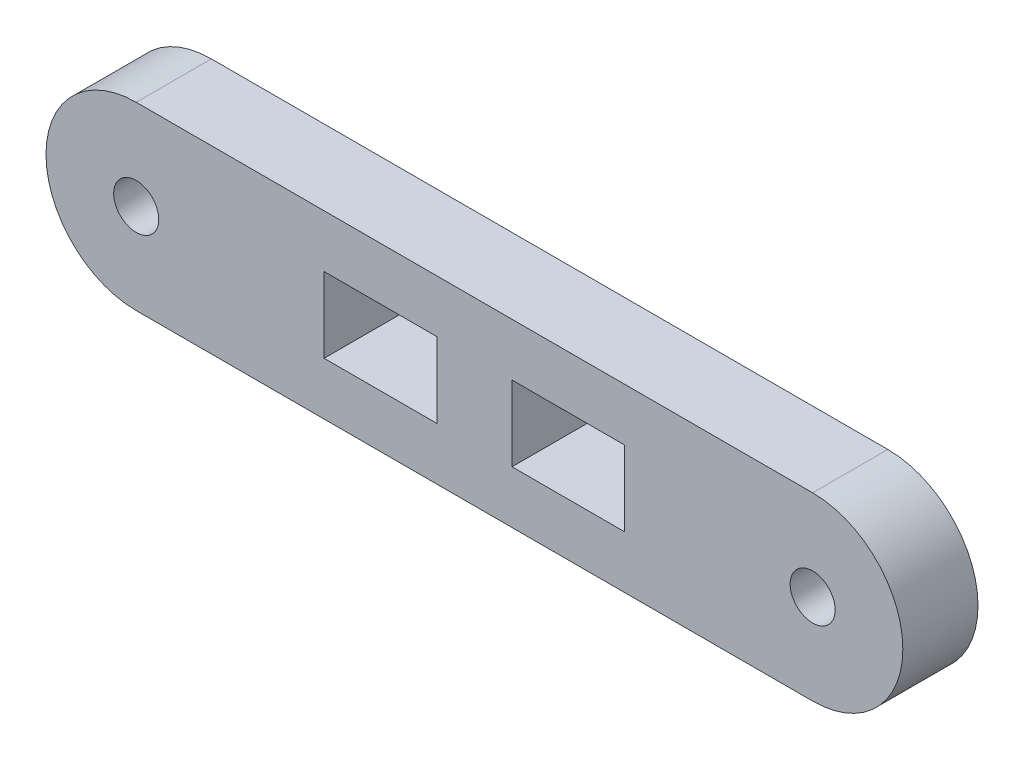
SolidWorks part; units mm, degrees
ref_plane "Plan de face" through (0, 0, 0) normal (0, 0, 1) x (1, 0, 0)
ref_plane "Plan de dessus" through (0, 0, 0) normal (0, 1, 0) x (1, 0, 0)
ref_plane "Plan de droite" through (0, 0, 0) normal (1, 0, 0) x (0, 0, -1)
sketch "Esquisse1" plane through (0, 0, 0) normal (0, 0, 1) x (1, 0, 0)
  line L0 (45, 0) -> (0, 0) construction
  line L1 (45, -6) -> (0, -6)
  line L2 (0, 0) -> (45, 0) construction
  line L3 (45, 6) -> (0, 6)
  line L4 (32.5, -2.5) -> (25, -2.5)
  line L5 (25, -2.5) -> (25, 2.5)
  line L6 (25, 2.5) -> (32.5, 2.5)
  line L7 (32.5, 2.5) -> (32.5, -2.5)
  line L8 (12.5, 2.5) -> (12.5, -2.5)
  line L9 (20, 2.5) -> (12.5, 2.5)
  line L10 (20, -2.5) -> (20, 2.5)
  line L11 (12.5, -2.5) -> (20, -2.5)
  line L12 (22.5, 6) -> (22.5, -6) construction
  arc A0 (45, -6) -> (45, 6) centre (45, 0) ccw
  arc A1 (0, 6) -> (0, -6) centre (0, 0) ccw
  circle A5 centre (45, 0) radius 1.5
  circle A6 centre (0, 0) radius 1.5
  point P0 (22.5, 0)
  dimension "D1" = 45
  dimension "D2" = 3
  dimension "D3" = 6
  dimension "D4" = 2.5
  dimension "D6" = 7.5
  dimension "D7" = 5
extrude "Boss.-Extru.1" add sketch "Esquisse1" along normal blind 5
